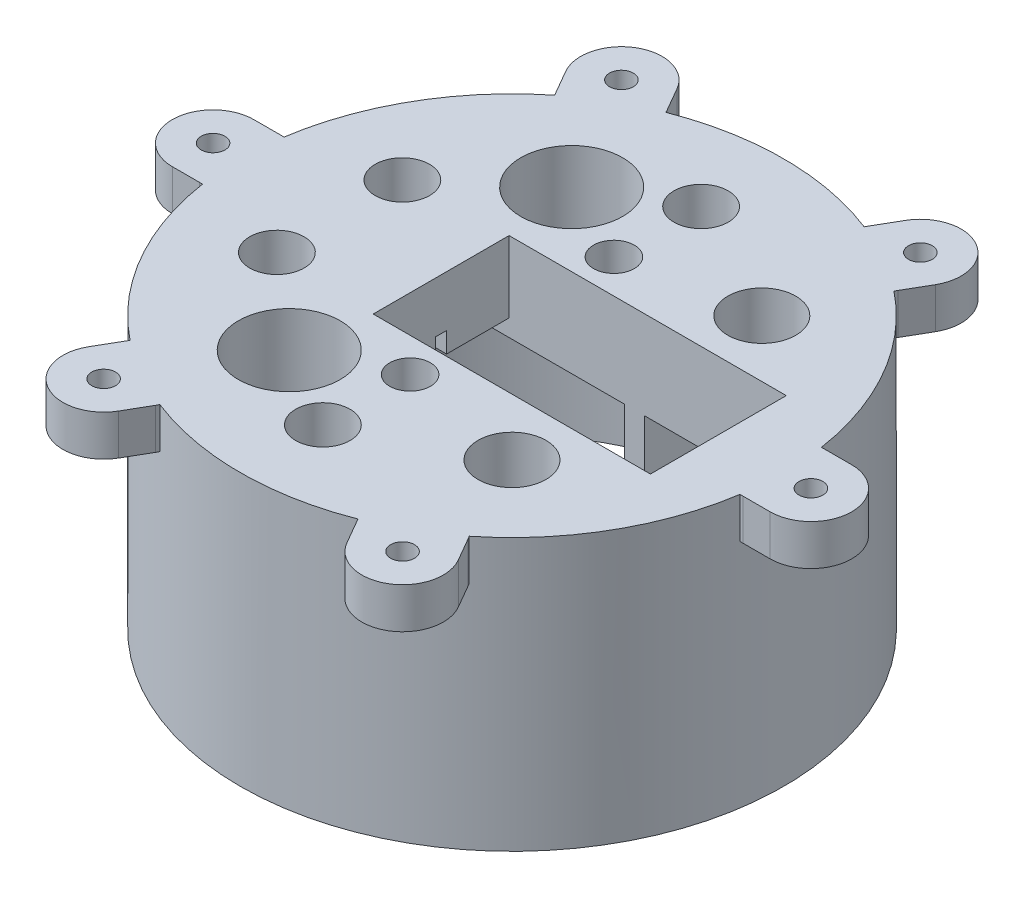
SolidWorks part; units mm, degrees
ref_plane "Front Plane" through (0, 0, 0) normal (0, 0, 1) x (1, 0, 0)
ref_plane "Top Plane" through (0, 0, 0) normal (0, 1, 0) x (1, 0, 0)
ref_plane "Right Plane" through (0, 0, 0) normal (1, 0, 0) x (0, 0, -1)
sketch "Sketch1" plane through (0, 0, 0) normal (0, 1, 0) x (1, 0, 0)
  line L0 (-43.0464, 0) -> (41.9462, 0) construction
  line L1 (0, 43.1152) -> (0, -41.8775) construction
  circle A1 centre (0, 0) radius 40
  dimension "D2" = 80
extrude "Boss-Extrude1" add sketch "Sketch1" along normal blind 40
sketch "Sketch2" plane through (0, 0, 0) normal (0, -1, 0) x (1, 0, 0)
  circle A0 centre (0, 0) radius 35
  dimension "D1" = 70
extrude "Cut-Extrude1" cut sketch "Sketch2" against normal blind 27
sketch "Sketch3" plane through (0, 27, 0) normal (0, -1, 0) x (1, 0, 0)
  line L0 (35, 0) -> (-35, 0) construction
  line L1 (0, -35) -> (0, 35) construction
  line L3 (37.5324, -10) -> (-17.4676, -10)
  line L4 (37.5324, -10) -> (37.5324, 10)
  line L5 (37.5324, 10) -> (-17.4676, 10)
  line L6 (-17.4676, -10) -> (-17.4676, 10)
  circle A0 centre (0, 0) radius 35 construction
  circle A1 centre (0, 0) radius 35 construction
  dimension "D1" = 20
  dimension "D2" = 55
  dimension "D3" = 10
  dimension "D4" = 37.5324
extrude "Cut-Extrude2" cut sketch "Sketch3" against normal blind 2.5 and the other way up to next
sketch "Sketch4" plane through (0, 29.5, 0) normal (0, -1, 0) x (1, 0, 0)
  line L0 (37.5324, 0) -> (-17.4676, 0) construction
  line L1 (37.5324, 10) -> (37.5324, -10) construction
  line L2 (-17.4676, 10) -> (-17.4676, -10) construction
  line L3 (0, -10) -> (0, 10) construction
  line L4 (-17.4676, -10) -> (33.541, -10) construction
  line L5 (33.541, 10) -> (-17.4676, 10) construction
  line L7 (30.3722, -10) -> (-10.4278, -10)
  line L8 (30.3722, -10) -> (30.3722, 10)
  line L9 (30.3722, 10) -> (-10.4278, 10)
  line L10 (-10.4278, -10) -> (-10.4278, 10)
  dimension "D1" = 20
  dimension "D2" = 40.8
  dimension "D3" = 30.3722
  dimension "D4" = 10
extrude "Cut-Extrude3" cut sketch "Sketch4" against normal blind 10.5
sketch "Sketch8" plane through (0, 27, 0) normal (0, -1, 0) x (1, 0, 0)
  line L0 (-17.4676, 0) -> (-35, 0) construction
  line L1 (-17.4676, 10) -> (-17.4676, -10) construction
  line L2 (8.0367, 10) -> (8.0367, 34.0648) construction
  line L3 (33.541, 10) -> (-17.4676, 10) construction
  line L4 (8.0367, -10) -> (8.0367, -29.3194) construction
  line L5 (-17.4676, -10) -> (33.541, -10) construction
  line L6 (6.5367, 10) -> (6.5367, 34.3842)
  line L7 (9.5367, 10) -> (9.5367, 33.6757)
  line L8 (9.5367, 10) -> (6.5367, 10)
  line L9 (9.5367, -10) -> (6.5367, -10)
  line L10 (6.5367, -10) -> (6.5367, -34.3842)
  line L11 (9.5367, -10) -> (9.5367, -33.6757)
  line L12 (-17.4676, 1.5) -> (-34.9678, 1.5)
  line L13 (-17.4676, -1.5) -> (-34.9678, -1.5)
  line L14 (-17.4676, 1.5) -> (-17.4676, -1.5)
  arc A0 (33.541, 10) -> (33.541, -10) centre (0, 0) ccw construction
  arc A1 (9.5367, 33.6757) -> (6.5367, 34.3842) centre (7.9531, 33.6757) ccw
  arc A2 (9.5367, -33.6757) -> (6.5367, -34.3842) centre (7.9531, -33.6757) cw
  arc A3 (-34.9678, 1.5) -> (-34.9678, -1.5) centre (-34.9678, 0) ccw
  dimension "D3" = 1.5
  dimension "D1" = 1.5
  dimension "D2" = 1.5
  dimension "D4" = 1.5
extrude "Boss-Extrude2" add sketch "Sketch8" along normal through all
sketch "Sketch13" plane through (0, 27, 0) normal (0, -1, 0) x (1, 0, 0)
  line L0 (0, 0) -> (0, 35) construction
  line L1 (0, 0) -> (-17.5, 30.3109) construction
  line L2 (0, 0) -> (-41.2446, 0) construction
  line L3 (-32.8892, 11.9707) -> (0, 0) construction
  line L5 (0, 0) -> (24.7487, 24.7487) construction
  arc A0 (6.5367, 34.3842) -> (-34.9678, 1.5) centre (0, 0) ccw construction
  circle A1 centre (-12, 20.7846) radius 7.5
  circle A2 centre (-25.3717, 9.2345) radius 4
  arc A3 (33.541, 10) -> (9.5367, 33.6757) centre (0, 0) ccw construction
  circle A4 centre (18.3848, 18.3848) radius 5
  circle A5 centre (18.3848, -18.3848) radius 5
  circle A6 centre (-12, -20.7846) radius 7.5
  circle A7 centre (-25.3717, -9.2345) radius 4
  circle A8 centre (0, -15) radius 3
  circle A9 centre (0, -27.8351) radius 4
  circle A10 centre (0, 27.8351) radius 4
  circle A11 centre (0, 15) radius 3
  dimension "D3" = 15
  dimension "D6" = 8
  dimension "D8" = 10
  dimension "D10" = 8
  dimension "D11" = 6
  dimension "D1" = 30
  dimension "D2" = 20
  dimension "D4" = 27
  dimension "D5" = 24
  dimension "D7" = 45
  dimension "D9" = 26
  dimension "D12" = 15
extrude "Cut-Extrude7" cut sketch "Sketch13" against normal through all
sketch "Sketch15" plane through (0, 0, -1.5) normal (0, 0, -1) x (-1, 0, 0)
  line L0 (34.9678, 0) -> (17.4676, 27)
  line L1 (17.4676, 27) -> (17.4676, 0)
  line L3 (17.4676, 0) -> (34.9678, 0)
extrude "Cut-Extrude8" cut sketch "Sketch15" against normal blind 3
sketch "Sketch16" plane through (0, 29.5, 0) normal (0, -1, 0) x (1, 0, 0)
  line L0 (-17.4676, 0) -> (37.5324, 0) construction
  line L1 (-17.4676, 10) -> (-17.4676, -10) construction
  line L2 (37.5324, -10) -> (37.5324, 10) construction
  line L3 (30.3722, -0.8) -> (37.5324, -0.8)
  line L4 (-10.4278, -0.8) -> (-17.4676, -0.8)
  line L5 (-10.4278, 10) -> (-10.4278, -10) construction
  line L6 (-10.4278, 0.8) -> (-17.4676, 0.8)
  line L7 (-17.4676, 0.8) -> (-17.4676, -0.8)
  line L8 (-10.4278, 0.8) -> (-10.4278, -0.8)
  line L9 (30.3722, -10) -> (30.3722, 10) construction
  line L10 (30.3722, 0.8) -> (37.5324, 0.8)
  line L11 (37.5324, 0.8) -> (37.5324, -0.8)
  line L12 (30.3722, 0.8) -> (30.3722, -0.8)
  dimension "D1" = 0.8
extrude "Cut-Extrude10" cut sketch "Sketch16" against normal blind 3
sketch "Sketch24" plane through (0, 40, 0) normal (0, 1, 0) x (1, 0, 0)
  line L0 (40, 0) -> (44, 0) construction
  line L1 (40, 6) -> (44, 6)
  line L2 (40, -6) -> (44, -6)
  line L3 (25.1962, -31.641) -> (27.1962, -35.1051)
  line L4 (14.8038, -37.641) -> (16.8038, -41.1051)
  line L5 (20, -34.641) -> (22, -38.1051) construction
  line L6 (-14.8038, -37.641) -> (-16.8038, -41.1051)
  line L7 (-25.1962, -31.641) -> (-27.1962, -35.1051)
  line L8 (-20, -34.641) -> (-22, -38.1051) construction
  line L9 (-40, -6) -> (-44, -6)
  line L10 (-40, 6) -> (-44, 6)
  line L11 (-40, 0) -> (-44, 0) construction
  line L12 (-25.1962, 31.641) -> (-27.1962, 35.1051)
  line L13 (-14.8038, 37.641) -> (-16.8038, 41.1051)
  line L14 (-20, 34.641) -> (-22, 38.1051) construction
  line L15 (14.8038, 37.641) -> (16.8038, 41.1051)
  line L16 (25.1962, 31.641) -> (27.1962, 35.1051)
  line L17 (20, 34.641) -> (22, 38.1051) construction
  arc A0 (39.55, -5.9831) -> (39.55, 5.9831) centre (0, 0) ccw
  arc A1 (40, 6) -> (39.55, 5.9831) centre (40, 0) ccw
  arc A2 (44, -6) -> (44, 6) centre (44, 0) ccw
  arc A3 (39.55, -5.9831) -> (40, -6) centre (40, 0) ccw
  arc A4 (14.5935, -37.2429) -> (24.9565, -31.2598) centre (0, 0) ccw
  arc A5 (25.1962, -31.641) -> (24.9565, -31.2598) centre (20, -34.641) ccw
  arc A6 (16.8038, -41.1051) -> (27.1962, -35.1051) centre (22, -38.1051) ccw
  arc A7 (14.5935, -37.2429) -> (14.8038, -37.641) centre (20, -34.641) ccw
  arc A8 (-24.9565, -31.2598) -> (-14.5935, -37.2429) centre (0, 0) ccw
  arc A9 (-14.8038, -37.641) -> (-14.5935, -37.2429) centre (-20, -34.641) ccw
  arc A10 (-27.1962, -35.1051) -> (-16.8038, -41.1051) centre (-22, -38.1051) ccw
  arc A11 (-24.9565, -31.2598) -> (-25.1962, -31.641) centre (-20, -34.641) ccw
  arc A12 (-39.55, 5.9831) -> (-39.55, -5.9831) centre (0, 0) ccw
  arc A13 (-40, -6) -> (-39.55, -5.9831) centre (-40, 0) ccw
  arc A14 (-44, 6) -> (-44, -6) centre (-44, 0) ccw
  arc A15 (-39.55, 5.9831) -> (-40, 6) centre (-40, 0) ccw
  arc A16 (-14.5935, 37.2429) -> (-24.9565, 31.2598) centre (0, 0) ccw
  arc A17 (-25.1962, 31.641) -> (-24.9565, 31.2598) centre (-20, 34.641) ccw
  arc A18 (-16.8038, 41.1051) -> (-27.1962, 35.1051) centre (-22, 38.1051) ccw
  arc A19 (-14.5935, 37.2429) -> (-14.8038, 37.641) centre (-20, 34.641) ccw
  arc A20 (24.9565, 31.2598) -> (14.5935, 37.2429) centre (0, 0) ccw
  arc A21 (14.8038, 37.641) -> (14.5935, 37.2429) centre (20, 34.641) ccw
  arc A22 (27.1962, 35.1051) -> (16.8038, 41.1051) centre (22, 38.1051) ccw
  arc A23 (24.9565, 31.2598) -> (25.1962, 31.641) centre (20, 34.641) ccw
  point P5 (42, 0)
  point P15 (21, -36.3731)
  point P24 (-21, -36.3731)
  point P33 (-42, 0)
  point P42 (-21, 36.3731)
  point P51 (21, 36.3731)
  point P58 (0, 0)
  dimension "D1" = 6
  dimension "D2" = 4
  dimension "D3" = 6
extrude "Boss-Extrude6" add sketch "Sketch24" against normal blind 6
sketch "Sketch25" plane through (0, 34, 0) normal (0, -1, 0) x (1, 0, 0)
  circle A0 centre (44, 0) radius 1.75
  circle A1 centre (22, -38.1051) radius 1.75
  circle A2 centre (-22, -38.1051) radius 1.75
  circle A3 centre (-44, 0) radius 1.75
  circle A4 centre (-22, 38.1051) radius 1.75
  circle A5 centre (22, 38.1051) radius 1.75
  point P15 (0, 0)
  dimension "D1" = 3.5
  dimension "D2" = 6
extrude "Cut-Extrude12" cut sketch "Sketch25" against normal through all
sketch "Sketch26" plane through (0, 34, 0) normal (0, -1, 0) x (1, 0, 0)
  line L0 (23.7321, -41.1051) -> (25.4641, -38.1051)
  line L1 (47.4641, 0) -> (45.7321, 3)
  line L2 (45.7321, 3) -> (42.2679, 3)
  line L3 (42.2679, 3) -> (40.5359, 0)
  line L4 (40.5359, 0) -> (42.2679, -3)
  line L5 (42.2679, -3) -> (45.7321, -3)
  line L6 (45.7321, -3) -> (47.4641, 0)
  line L7 (25.4641, -38.1051) -> (23.7321, -35.1051)
  line L8 (23.7321, -35.1051) -> (20.2679, -35.1051)
  line L9 (20.2679, -35.1051) -> (18.5359, -38.1051)
  line L10 (18.5359, -38.1051) -> (20.2679, -41.1051)
  line L11 (20.2679, -41.1051) -> (23.7321, -41.1051)
  line L12 (-23.7321, -41.1051) -> (-20.2679, -41.1051)
  line L13 (-20.2679, -41.1051) -> (-18.5359, -38.1051)
  line L14 (-18.5359, -38.1051) -> (-20.2679, -35.1051)
  line L15 (-20.2679, -35.1051) -> (-23.7321, -35.1051)
  line L16 (-23.7321, -35.1051) -> (-25.4641, -38.1051)
  line L17 (-25.4641, -38.1051) -> (-23.7321, -41.1051)
  line L18 (-47.4641, 0) -> (-45.7321, -3)
  line L19 (-45.7321, -3) -> (-42.2679, -3)
  line L20 (-42.2679, -3) -> (-40.5359, 0)
  line L21 (-40.5359, 0) -> (-42.2679, 3)
  line L22 (-42.2679, 3) -> (-45.7321, 3)
  line L23 (-45.7321, 3) -> (-47.4641, 0)
  line L24 (-23.7321, 41.1051) -> (-25.4641, 38.1051)
  line L25 (-25.4641, 38.1051) -> (-23.7321, 35.1051)
  line L26 (-23.7321, 35.1051) -> (-20.2679, 35.1051)
  line L27 (-20.2679, 35.1051) -> (-18.5359, 38.1051)
  line L28 (-18.5359, 38.1051) -> (-20.2679, 41.1051)
  line L29 (-20.2679, 41.1051) -> (-23.7321, 41.1051)
  line L30 (23.7321, 41.1051) -> (20.2679, 41.1051)
  line L31 (20.2679, 41.1051) -> (18.5359, 38.1051)
  line L32 (18.5359, 38.1051) -> (20.2679, 35.1051)
  line L33 (20.2679, 35.1051) -> (23.7321, 35.1051)
  line L34 (23.7321, 35.1051) -> (25.4641, 38.1051)
  line L35 (25.4641, 38.1051) -> (23.7321, 41.1051)
  circle A0 centre (44, 0) radius 3 construction
  circle A1 centre (22, -38.1051) radius 3 construction
  circle A2 centre (-22, -38.1051) radius 3 construction
  circle A3 centre (-44, 0) radius 3 construction
  circle A4 centre (-22, 38.1051) radius 3 construction
  circle A5 centre (22, 38.1051) radius 3 construction
  point P51 (0, 0)
  dimension "D1" = 6
  dimension "D2" = 6
extrude "Cut-Extrude13" cut sketch "Sketch26" against normal blind 3
